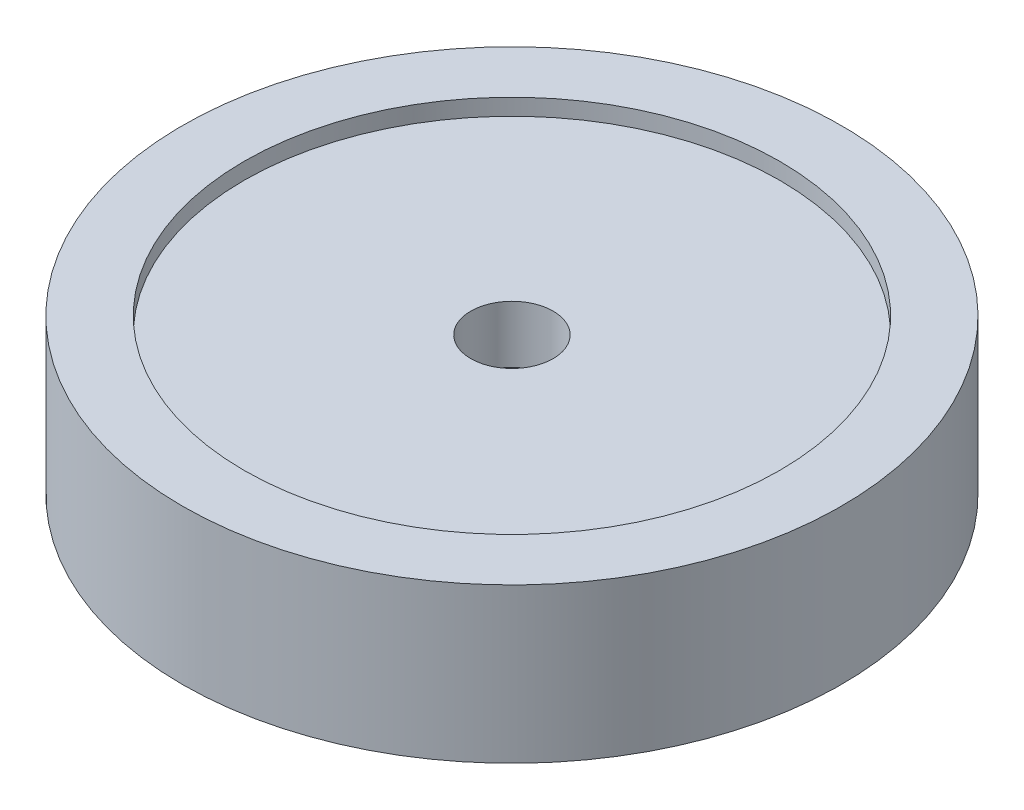
SolidWorks part; units mm, degrees
ref_plane "Front Plane" through (0, 0, 0) normal (0, 0, 1) x (1, 0, 0)
ref_plane "Top Plane" through (0, 0, 0) normal (0, 1, 0) x (1, 0, 0)
ref_plane "Right Plane" through (0, 0, 0) normal (1, 0, 0) x (0, 0, -1)
sketch "Sketch1" plane through (0, 0, 0) normal (0, 1, 0) x (1, 0, 0)
  line L0 (0, 0) -> (0, 10) construction
  line L5 (-11.5, 11.5) -> (11.5, 11.5)
  line L6 (-10, 10) -> (10, 10)
  line L7 (-10, 10) -> (-10, -30)
  line L8 (-10, -30) -> (10, -30)
  line L9 (10, 10) -> (10, -30)
  line L10 (11.5, 11.5) -> (11.5, -31.5)
  line L11 (-11.5, -31.5) -> (11.5, -31.5)
  line L12 (-11.5, 11.5) -> (-11.5, -31.5)
  circle A0 centre (0, 0) radius 40
  circle A1 centre (0, 0) radius 5
  circle A2 centre (0, 0) radius 32.5
  point P14 (0, 10)
  dimension "D2" = 80
  dimension "D6" = 10
  dimension "D7" = 65
  dimension "D1" = 1.5
  dimension "D3" = 10
  dimension "D4" = 40
  dimension "D5" = 20
extrude "Boss-Extrude1" add sketch "Sketch1" along normal blind 18.75 contours A0
extrude "Cut-Extrude1" cut sketch "Sketch1<3>" along normal blind 9.8 contours L12 L11 L10 L5
sketch "Sketch1<3>" plane through (0, 0, 0) normal (0, 1, 0) x (1, 0, 0) same geometry as "Sketch1"
extrude "Cut-Extrude2" cut sketch "Sketch1<4>" against normal through all both and the other way through all contours A1
sketch "Sketch1<4>" plane through (0, 0, 0) normal (0, 1, 0) x (1, 0, 0) same geometry as "Sketch1"
extrude "Cut-Extrude3" cut sketch "Sketch1<5>" against normal blind 2 from surface contours A2 starting at face at (0, 18.75, 5)
sketch "Sketch1<5>" plane through (0, 0, 0) normal (0, 1, 0) x (1, 0, 0) same geometry as "Sketch1"
